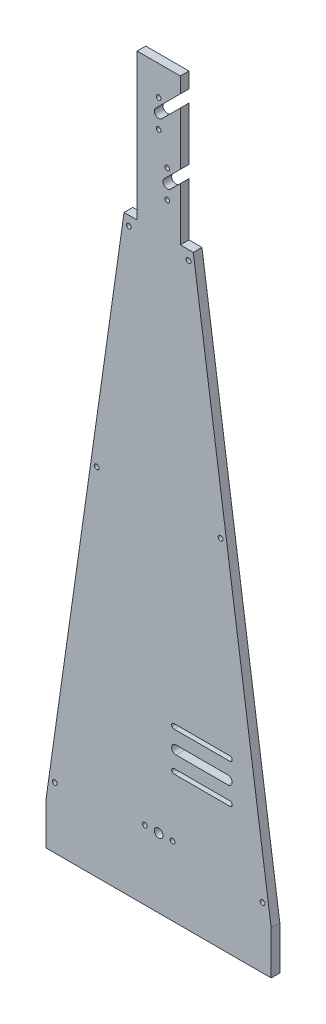
SolidWorks part; units mm, degrees
ref_plane "Ebene vorne" through (0, 0, 0) normal (0, 0, 1) x (1, 0, 0)
ref_plane "Ebene oben" through (0, 0, 0) normal (0, 1, 0) x (1, 0, 0)
ref_plane "Ebene rechts" through (0, 0, 0) normal (1, 0, 0) x (0, 0, -1)
sketch "Skizze1" plane through (0, 0, 0) normal (0, 0, 1) x (1, 0, 0)
  line L0 (-40, 681) -> (-130, 50)
  line L1 (-263.5092, 681) -> (296.6943, 681) construction
  line L2 (0, 800) -> (0, 0)
  line L3 (-25, 800) -> (-25, 681)
  line L4 (-40, 681) -> (-25, 681)
  line L5 (0, 800) -> (0, 850)
  line L7 (-130, 0) -> (-130, 50)
  line L10 (40, 681) -> (25, 681)
  line L12 (-130, 0) -> (0, 0)
  line L13 (-32.9292, 681) -> (-123.0701, 49.0116) construction
  line L14 (-33.0701, 680.0116) -> (-123.0701, 49.0116) construction
  line L15 (-25, 800) -> (-25, 850)
  line L16 (-25, 850) -> (0, 850)
  point P2 (0, 800)
  point P4 (0, 681)
  point P8 (-40, 681)
  point P12 (-119.9898, 70.6083)
  point P18 (-71.4708, 410.7801)
  point P21 (-34.4874, 670.075)
  point P23 (0, 816)
  point P24 (0, 784)
  dimension "D2" = 25
  dimension "D5" = 50
  dimension "D6" = 130
  dimension "D1" = 800
  dimension "D3" = 119
  dimension "D4" = 40
  dimension "D8" = 50
  dimension "D9" = 16
  dimension "D10" = 16
  dimension "D7" = 7
extrude "Aufsatz-Linear austragen1" add sketch "Skizze1" along normal blind 10 contours L2 L12 L7 L0 L4 L3 L15 L16 L5
mirror "Spiegeln1" about plane through (0, 800, 10) normal (1, 0, 0) of "Aufsatz-Linear austragen1"
sketch "Skizze17" plane through (0, 0, 10) normal (0, 0, 1) x (1, 0, 0)
  line L0 (0, 800) -> (28.5355, 828.5355) construction
  line L1 (-3.5355, 803.5355) -> (25, 832.0711)
  line L2 (3.5355, 796.4645) -> (32.0711, 825)
  line L3 (-25, 850) -> (25, 850) construction
  line L4 (25, 850) -> (25, 681) construction
  line L5 (10, 734.4448) -> (28.5355, 752.9803) construction
  line L6 (6.4645, 737.9803) -> (25, 756.5159)
  line L7 (13.5355, 730.9093) -> (32.0711, 749.4448)
  line L8 (-25, 850) -> (0, 850) construction
  line L9 (10, 850) -> (10, 681) construction
  line L10 (-263.5092, 681) -> (296.6943, 681) construction
  arc A0 (-3.5355, 803.5355) -> (3.5355, 796.4645) centre (0, 800) ccw
  arc A1 (32.0711, 825) -> (25, 832.0711) centre (28.5355, 828.5355) ccw
  circle A2 centre (0, 816) radius 2.75
  circle A3 centre (0, 784) radius 2.75
  arc A4 (6.4645, 737.9803) -> (13.5355, 730.9093) centre (10, 734.4448) ccw
  arc A5 (32.0711, 749.4448) -> (25, 756.5159) centre (28.5355, 752.9803) ccw
  circle A6 centre (10, 750.4448) radius 2.75
  circle A7 centre (10, 718.4448) radius 2.75
  point P2 (14.2678, 814.2678)
  point P20 (19.2678, 743.7126)
  dimension "D2" = 5
  dimension "D3" = 5.5
  dimension "D4" = 5.5
  dimension "D6" = 5
  dimension "D10" = 5.5
  dimension "D11" = 5.5
  dimension "D1" = 45
  dimension "D5" = 45
  dimension "D7" = 15
  dimension "D8" = 16
  dimension "D9" = 16
extrude "Schnitt-Linear austragen1" cut sketch "Skizze17" against normal blind 10
hole_wizard "Ø10.0 (10) Durchmesser Bohrung1" positions "Skizze6" profile "Skizze5" hole size "Ø10.0" standard "ISO" end condition through all
sketch "Skizze6" plane through (0, 0, 10) normal (0, 0, 1) x (1, 0, 0)
  line L0 (0, 800) -> (0, 0) construction
  line L1 (-130, 0) -> (130, 0) construction
  point P3 (0, 80)
  dimension "D1" = 80
sketch "Skizze5" plane through (0, 80, 10) normal (1, 0, 0) x (0, -1, 0)
  line L0 (0, 0) -> (0, 10)
  line L1 (0, 10) -> (5, 10)
  line L2 (5, 10) -> (5, 0)
  line L5 (5, 0) -> (0, 0)
  line L11 (0, -6.35) -> (0, 107.95) construction
  dimension "Bohrerdurchmesser" = 10
  dimension "Bohrungstiefe" = 10
hole_wizard "Ø5.5 (5.5) Durchmesser Bohrung2" positions "Skizze7" profile "Skizze8" hole size "Ø5.5" standard "ISO" end condition through all
sketch "Skizze7" plane through (0, 0, 10) normal (0, 0, 1) x (1, 0, 0)
  line L1 (0, 80) -> (-104.9668, 80) construction
  line L3 (0, 80) -> (96.42, 80) construction
  circle A0 centre (0, 80) radius 5 construction
  point P0 (-16, 80)
  point P4 (16, 80)
  dimension "D1" = 16
  dimension "D2" = 16
sketch "Skizze8" plane through (-16, 80, 10) normal (1, 0, 0) x (0, -1, 0)
  line L0 (0, 0) -> (0, 10)
  line L1 (0, 10) -> (2.75, 10)
  line L2 (2.75, 10) -> (2.75, 0)
  line L5 (2.75, 0) -> (0, 0)
  line L11 (0, -6.35) -> (0, 107.95) construction
  dimension "Bohrerdurchmesser" = 5.5
  dimension "Bohrungstiefe" = 10
hole_wizard "Ø10.0 (10) Durchmesser Langloch2" positions "Skizze9" profile "Skizze10" size "Ø10.0" standard "ISO" slot yes end condition through all
sketch "Skizze9" plane through (0, 0, 10) normal (0, 0, 1) x (1, 0, 0)
  line L0 (15, 173.191) -> (85, 173.191) construction
  line L1 (130, 0) -> (130, 50) construction
  point P0 (50, 173.191)
  dimension "D1" = 70
  dimension "D2" = 80
sketch "Skizze10" plane through (50, 173.191, 10) normal (1, 0, 0) x (0, -1, 0)
  line L0 (0, 0) -> (0, 10)
  line L1 (0, 10) -> (5, 10)
  line L2 (5, 10) -> (5, 0)
  line L5 (5, 0) -> (0, 0)
  line L11 (0, -6.35) -> (0, 107.95) construction
  dimension "Bohrerdurchmesser" = 10
  dimension "Bohrungstiefe" = 10
hole_wizard "Ø5.5 (5.5) Durchmesser Langloch2" positions "Skizze13" profile "Skizze14" size "Ø5.5" standard "ISO" slot yes end condition through all
sketch "Skizze13" plane through (0, 0, 10) normal (0, 0, 1) x (1, 0, 0)
  line L0 (15, 195.691) -> (85, 195.691) construction
  line L1 (50, 195.691) -> (50, 150.691) construction
  line L2 (130, 0) -> (130, 50) construction
  arc A0 (20, 178.191) -> (20, 168.191) centre (20, 173.191) ccw construction
  point P0 (50, 195.691)
  point P4 (50, 150.691)
  point P10 (15, 173.191)
  dimension "D1" = 70
  dimension "D2" = 22.5
  dimension "D3" = 22.5
  dimension "D4" = 80
sketch "Skizze14" plane through (50, 195.691, 10) normal (1, 0, 0) x (0, -1, 0)
  line L0 (0, 0) -> (0, 10)
  line L1 (0, 10) -> (2.75, 10)
  line L2 (2.75, 10) -> (2.75, 0)
  line L5 (2.75, 0) -> (0, 0)
  line L11 (0, -6.35) -> (0, 107.95) construction
  dimension "Bohrerdurchmesser" = 5.5
  dimension "Bohrungstiefe" = 10
hole_wizard "Ø5.5 (5.5) Durchmesser Bohrung3" positions "Skizze19" profile "Skizze18" hole size "Ø5.5" standard "ISO" end condition through all
sketch "Skizze19" plane through (0, 0, 10) normal (0, 0, 1) x (1, 0, 0)
  point P0 (-34.4874, 670.075)
  point P3 (-71.4708, 410.7801)
  point P6 (-119.9898, 70.6083)
sketch "Skizze18" plane through (-34.4874, 670.075, 10) normal (1, 0, 0) x (0, -1, 0)
  line L0 (0, 0) -> (0, 10)
  line L1 (0, 10) -> (2.75, 10)
  line L2 (2.75, 10) -> (2.75, 0)
  line L5 (2.75, 0) -> (0, 0)
  line L11 (0, -6.35) -> (0, 107.95) construction
  dimension "Bohrerdurchmesser" = 5.5
  dimension "Bohrungstiefe" = 10
mirror "Spiegeln2" about plane through (0, 0, 0) normal (1, 0, 0) of "Ø5.5 (5.5) Durchmesser Bohrung3"
